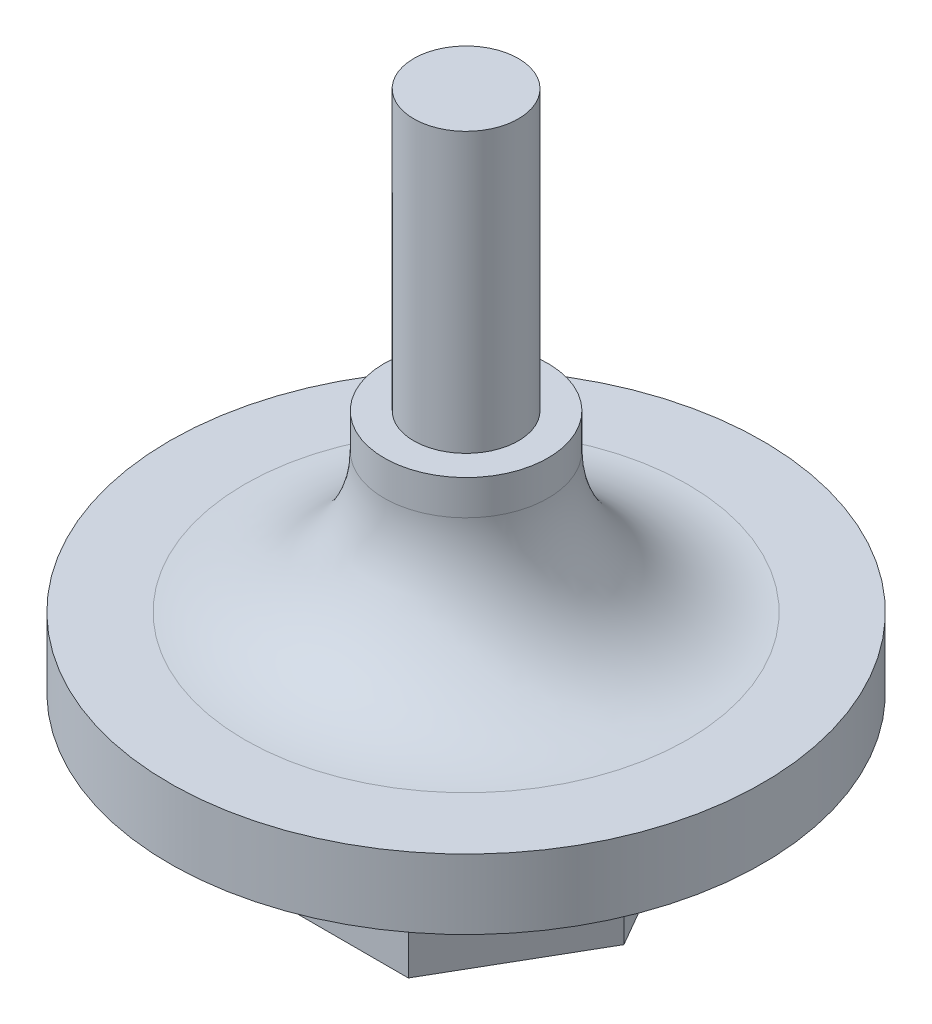
SolidWorks part; units mm, degrees
ref_plane "Front Plane" through (0, 0, 0) normal (0, 0, 1) x (1, 0, 0)
ref_plane "Top Plane" through (0, 0, 0) normal (0, 1, 0) x (1, 0, 0)
ref_plane "Right Plane" through (0, 0, 0) normal (1, 0, 0) x (0, 0, -1)
sketch "Sketch1" plane through (0, 0, 0) normal (0, 0, 1) x (1, 0, 0)
  line L0 (0, 0) -> (13.5, 0)
  line L1 (13.5, 0) -> (13.5, 3.175)
  line L2 (13.5, 3.175) -> (10.08, 3.175)
  line L3 (3.73, 9.525) -> (3.73, 11.1125)
  line L4 (3.73, 11.1125) -> (2.3813, 11.1125)
  line L5 (2.3813, 11.1125) -> (2.3813, 23.8125)
  line L6 (2.3813, 23.8125) -> (0, 23.8125)
  line L7 (0, 23.8125) -> (0, 0) construction
  line L8 (0, 0) -> (0, 23.8125)
  arc A1 (10.08, 3.175) -> (3.73, 9.525) centre (10.08, 9.525) cw
  point P9 (10.5, 3.175)
  point P12 (0, 0)
  point P13 (2.3813, 7.9375)
  point P14 (6.8813, 7.9375)
  dimension "D6" = 6.35
  dimension "D1" = 4.7625
  dimension "D2" = 7.9375
  dimension "D3" = 3.175
  dimension "D4" = 27
  dimension "D5" = 3.73
  dimension "D7" = 12.7
revolve "Revolve1" add sketch "Sketch1" angle 360 about L7
sketch "Sketch2" plane through (0, 0, 0) normal (0, -1, 0) x (1, 0, 0)
  line L1 (7.1857, 0) -> (3.5929, 6.223)
  line L2 (3.5929, 6.223) -> (-3.5929, 6.223)
  line L3 (-3.5929, 6.223) -> (-7.1857, 0)
  line L4 (-7.1857, 0) -> (-3.5929, -6.223)
  line L5 (-3.5929, -6.223) -> (3.5929, -6.223)
  line L6 (3.5929, -6.223) -> (7.1857, 0)
  circle A0 centre (0, 0) radius 6.223 construction
  dimension "D1" = 12.446
extrude "Boss-Extrude1" add sketch "Sketch2" along normal blind 6.35
